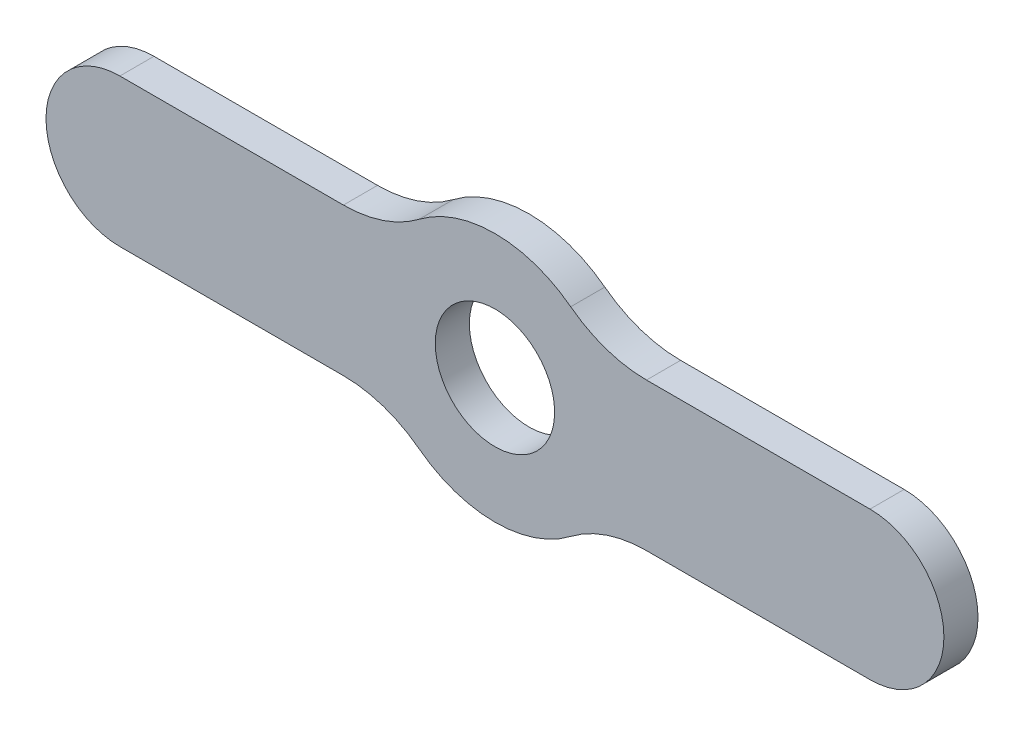
SolidWorks part; units mm, degrees
ref_plane "Plano frontal" through (0, 0, 0) normal (0, 0, 1) x (1, 0, 0)
ref_plane "Plano superior" through (0, 0, 0) normal (0, 1, 0) x (1, 0, 0)
ref_plane "Plano direito" through (0, 0, 0) normal (1, 0, 0) x (0, 0, -1)
sketch "Esboço1" plane through (0, 0, 0) normal (0, 0, 1) x (1, 0, 0)
  line L0 (-33, 6.5) -> (-8.8741, 6.5)
  line L5 (8.8741, 6.5) -> (33, 6.5)
  line L6 (-33, -6.5) -> (-8.8741, -6.5)
  line L7 (8.8741, -6.5) -> (33, -6.5)
  arc A2 (33, 6.5) -> (33, -6.5) centre (33, 0) cw
  arc A3 (-33, 6.5) -> (-33, -6.5) centre (-33, 0) ccw
  arc A4 (0, 11) -> (8.8741, 6.5) centre (0, 0) cw
  arc A5 (0, 11) -> (-8.8741, 6.5) centre (0, 0) ccw
  arc A6 (0, -11) -> (8.8741, -6.5) centre (0, 0) ccw
  arc A7 (0, -11) -> (-8.8741, -6.5) centre (0, 0) cw
  point P4 (0, 0)
base flange "Flange-base1" sketch "Esboço1" thickness 3 reverse thickness direction no parameters "D1"=10
fillet "Filete1" radius 11 1 edges at (-8.8741, 6.5, -1.5)
fillet "Filete2" radius 11 3 edges at (8.8741, 6.5, -1.5) (-8.8741, -6.5, -1.5) (8.8741, -6.5, -1.5)
sketch "Esboço2" plane through (0, 0, -3) normal (0, 0, -1) x (-1, 0, 0)
  circle A0 centre (0, 0) radius 5.25
extrude "Corte-extrusão1" cut sketch "Esboço2" against normal up to next normal cut yes
sketch "Curva-Linhas1" [suppressed] plane through (0, 0, 0) normal (0, 1, 0) x (1, 0, 0)
sketch "Caixa delimitadora1" [suppressed] plane through (0, 0, 0) normal (0, 1, 0) x (1, 0, 0)
sheet metal parameters "Chapa metálica1" thickness 3 parameters "D1"=10
flat pattern "Padrão-Plano1" [suppressed]
sketch "Curva-Linhas2" plane through (0, 0, 0) normal (0, 1, 0) x (1, 0, 0)
sketch3d "Caixa delimitadora2" [suppressed]
  line L0 (-70.3256, 16.2415, 0) -> (7.3256, 5.5528, 0) construction
  line L1 (-73.3256, -5.5528, 0) -> (4.3256, -16.2415, 0) construction
  line L2 (-70.3256, 16.2415, 0) -> (-73.3256, -5.5528, 0) construction
  line L3 (7.3256, 5.5528, 0) -> (4.3256, -16.2415, 0) construction
sheet metal parameters "Chapa metálica2" thickness 3 parameters "D1"=10
flat pattern "Padrão-Plano1"
sketch "Curva-Linhas2" plane through (0, 0, 0) normal (0, 1, 0) x (1, 0, 0)
sketch3d "Caixa delimitadora2" [suppressed]
  line L0 (-70.3256, 16.2415, 0) -> (7.3256, 5.5528, 0) construction
  line L1 (-73.3256, -5.5528, 0) -> (4.3256, -16.2415, 0) construction
  line L2 (-70.3256, 16.2415, 0) -> (-73.3256, -5.5528, 0) construction
  line L3 (7.3256, 5.5528, 0) -> (4.3256, -16.2415, 0) construction
